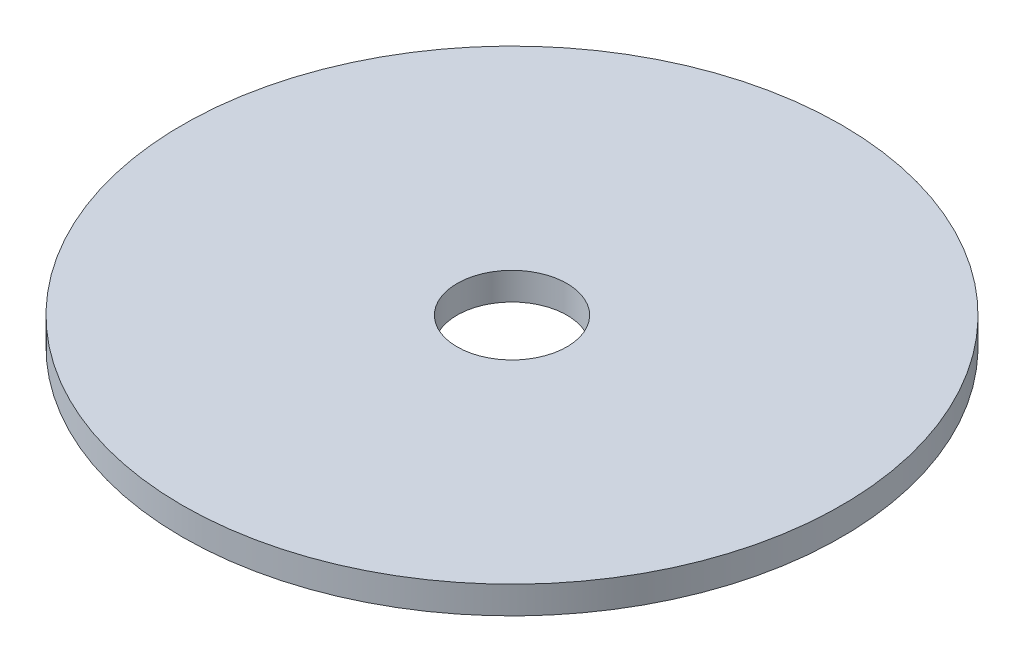
SolidWorks part; units mm, degrees
ref_plane "Front Plane" through (0, 0, 0) normal (0, 0, 1) x (1, 0, 0)
ref_plane "Top Plane" through (0, 0, 0) normal (0, 1, 0) x (1, 0, 0)
ref_plane "Right Plane" through (0, 0, 0) normal (1, 0, 0) x (0, 0, -1)
sketch "Sketch1" plane through (0, 0, 0) normal (0, 1, 0) x (1, 0, 0)
  circle A0 centre (0, 0) radius 38.1
  dimension "D1" = 76.2
extrude "Boss-Extrude1" add sketch "Sketch1" along normal blind 3.175
sketch "Sketch2" plane through (0, 3.175, 0) normal (0, 1, 0) x (1, 0, 0)
  circle A0 centre (0, 0) radius 6.35
  dimension "D1" = 12.7
extrude "Cut-Extrude1" cut sketch "Sketch2" against normal through all
